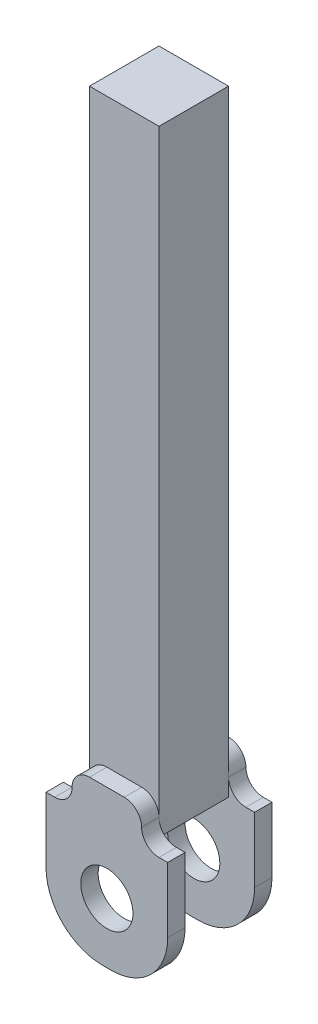
SolidWorks part; units mm, degrees
material "Chrome Stainless Steel"
ref_plane "Front Plane" through (0, 0, 0) normal (0, 0, 1) x (1, 0, 0)
ref_plane "Top Plane" through (0, 0, 0) normal (0, 1, 0) x (1, 0, 0)
ref_plane "Right Plane" through (0, 0, 0) normal (1, 0, 0) x (0, 0, -1)
sketch "Sketch1" plane through (0, 0, 0) normal (0, 1, 0) x (1, 0, 0)
  line L1 (-25.4, -25.4) -> (25.4, -25.4)
  line L2 (-25.4, -25.4) -> (-25.4, 25.4)
  line L3 (-25.4, 25.4) -> (25.4, 25.4)
  line L4 (25.4, -25.4) -> (25.4, 25.4)
  line L5 (-25.4, -25.4) -> (25.4, 25.4) construction
  line L6 (-25.4, 25.4) -> (25.4, -25.4) construction
  point P0 (0, 0)
  dimension "D1" = 50.8
  dimension "D2" = 50.8
extrude "Boss-Extrude1" add sketch "Sketch1" along normal blind 450
sketch "Sketch3" plane through (0, 0, 25.4) normal (0, 0, 1) x (1, 0, 0)
  line L0 (-25.4, 0) -> (-25.4, 25.4)
  line L1 (-44.45, 0) -> (-25.4, 0)
  line L2 (-44.45, 0) -> (-44.45, -88.9)
  line L3 (-44.45, -88.9) -> (44.45, -88.9)
  line L4 (44.45, 0) -> (44.45, -88.9)
  line L5 (-25.4, 450) -> (-25.4, 0) construction
  line L6 (-25.4, 25.4) -> (25.4, 25.4)
  line L7 (25.4, 450) -> (25.4, 0) construction
  line L8 (25.4, 25.4) -> (25.4, 0)
  line L9 (25.4, 0) -> (44.45, 0)
  line L10 (-25.4, 450) -> (25.4, 450) construction
  circle A0 centre (0, -45) radius 19.05
  point P4 (0, -88.9)
  point P13 (0, 450)
  dimension "D3" = 38.1
  dimension "D1" = 88.9
  dimension "D2" = 88.9
  dimension "D4" = 25.4
  dimension "D5" = 495
extrude "Boss-Extrude2" add sketch "Sketch3" along normal blind 12.7
ref_plane "Plane1" through (0, 0, 0) normal (0, 0, 1) x (1, 0, 0)
mirror "Mirror1" about plane through (0, 0, 0) normal (0, 0, 1) of "Boss-Extrude2"
fillet "Fillet1" radius 12.7 8 edges at (25.4, 25.4, -31.75) (25.4, 25.4, 31.75) (25.4, 0, 31.75) (25.4, 0, -31.75) (-25.4, 25.4, 31.75) (-25.4, 25.4, -31.75) (-25.4, 0, -31.75) (-25.4, 0, 31.75)
fillet "Fillet3" radius 41.275 4 edges at (-44.45, -88.9, -31.75) (-44.45, -88.9, 31.75) (44.45, -88.9, 31.75) (44.45, -88.9, -31.75)
sketch "Sketch4" plane through (0, 0, 0) normal (0, 0, 1) x (1, 0, 0)
  point P0 (0, -45)
  point P1 (0, 0)
